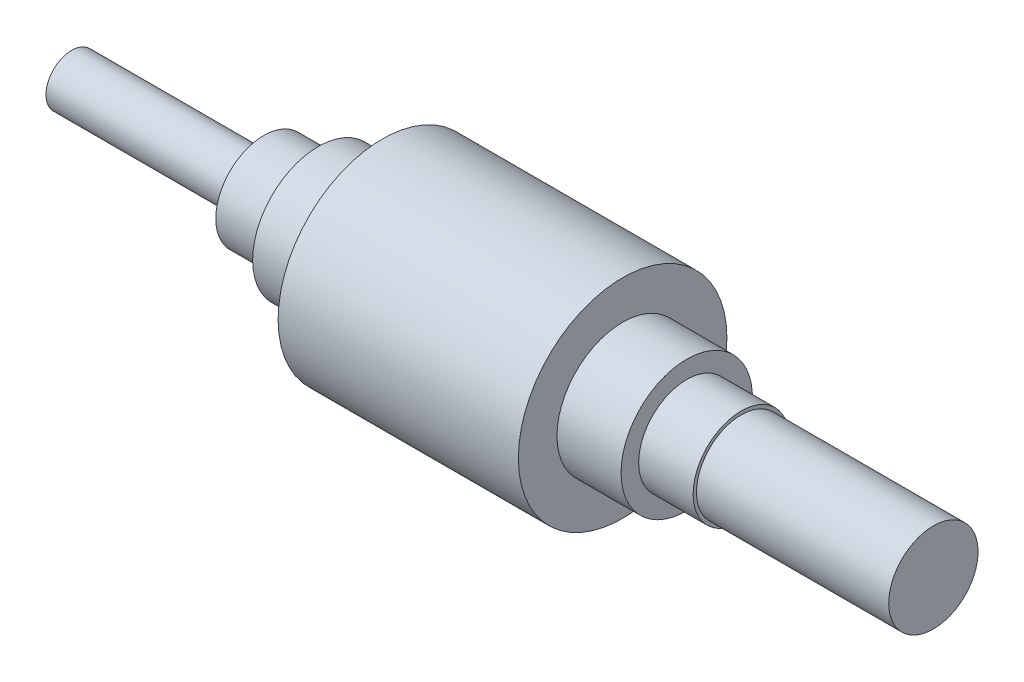
SolidWorks part; units mm, degrees
ref_plane "Ön Düzlem" through (0, 0, 0) normal (0, 0, 1) x (1, 0, 0)
ref_plane "Üst Düzlem" through (0, 0, 0) normal (0, 1, 0) x (1, 0, 0)
ref_plane "Sağ Düzlem" through (0, 0, 0) normal (1, 0, 0) x (0, 0, -1)
sketch "Çizim1" plane through (0, 0, 0) normal (0, 0, 1) x (1, 0, 0)
  line L1 (30, 7.5) -> (38.5, 7.5)
  line L2 (38.5, 7.5) -> (38.5, 10.25)
  line L3 (38.5, 10.25) -> (48.5, 10.25)
  line L4 (48.5, 10.25) -> (48.5, 16.275)
  line L5 (48.5, 16.275) -> (86, 16.275)
  line L6 (86, 16.275) -> (86, 10.25)
  line L7 (86, 10.25) -> (96, 10.25)
  line L8 (96, 10.25) -> (96, 7.5)
  line L10 (134.5, 6.975) -> (134.5, 0)
  line L11 (0, 0) -> (50000, 0) construction
  line L12 (0, 0) -> (134.5, 0)
  line L13 (96, 7.5) -> (104.5, 7.5)
  line L14 (104.5, 7.5) -> (104.5, 6.975)
  line L15 (104.5, 6.975) -> (134.5, 6.975)
  line L16 (30, 7.5) -> (30, 4)
  line L17 (30, 4) -> (0, 4)
  line L18 (0, 4) -> (0, 0)
  point P13 (10.1128, 10)
  dimension "D2" = 7.5
  dimension "D3" = 10
  dimension "D4" = 10.25
  dimension "D5" = 37.5
  dimension "D6" = 6.975
  dimension "D7" = 7.5
  dimension "D8" = 16.275
  dimension "D9" = 10
  dimension "D10" = 8.5
  dimension "D11" = 10.25
  dimension "D12" = 30
  dimension "D13" = 8.5
  dimension "D14" = 30
  dimension "D15" = 4
revolve "Döndür1" add sketch "Çizim1" angle 360 about L11
